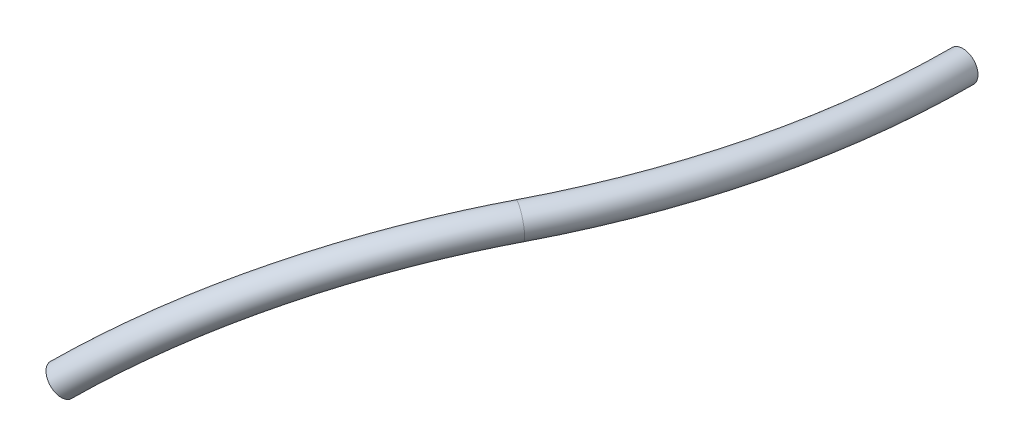
SolidWorks part; units mm, degrees
ref_plane "Front" through (0, 0, 0) normal (0, 0, 1) x (1, 0, 0)
ref_plane "Top" through (0, 0, 0) normal (0, 1, 0) x (1, 0, 0)
ref_plane "Right" through (0, 0, 0) normal (1, 0, 0) x (0, 0, -1)
sketch "Sketch1" plane through (0, 0, 0) normal (0, 0, 1) x (1, 0, 0)
  circle A0 centre (3583.5486, 6892.4155) radius 50.8
ref_plane "Plane1" through (-767.9169, 6367.643, 0) normal (0.1197, -0.9928, 0) x (0, 0, -1)
sketch "Sketch2" plane through (-767.9169, 6367.643, 0) normal (0.1197, -0.9928, 0) x (0, 0, -1)
  line L0 (0, 4382.9942) -> (-326.2728, 4382.9942) construction
  line L1 (-1154.8874, 4046.4415) -> (-1434.4794, 3868.3634) construction
  line L2 (-1154.8874, 4046.4415) -> (0, 4382.9942) construction
  line L3 (-577.4437, 4214.7179) -> (-601.4633, 4297.1418) construction
  arc A0 (0, 4382.9942) -> (-1154.8874, 4046.4415) centre (0, 2233.2082) ccw
  point P6 (-609.9931, 4294.6369)
  dimension "D1" = 1219.2
  dimension "D2" = 600.71
  dimension "D4" = 1524
  dimension "D3" = 85.8524
ref_plane "Plane2" through (-508.8422, 360.2726, -294.2875) normal (0.7381, -0.5226, 0.4269) x (-0.6491, -0.7226, 0.2377)
sketch "Sketch3" plane through (-508.8422, 360.2726, -294.2875) normal (0.7381, -0.5226, 0.4269) x (-0.6491, -0.7226, 0.2377)
  line L0 (-6786.2097, -3509.4251) -> (-6589.5927, -3776.3058) construction
  line L1 (-5763.7034, -4110.8775) -> (-2094.3697, -4581.5268) construction
  line L2 (-6786.2097, -3509.4251) -> (-5763.7034, -4110.8775) construction
  line L3 (-6274.9565, -3810.1513) -> (-6336.565, -3914.8895) construction
  arc A0 (-6786.2097, -3509.4251) -> (-5763.7034, -4110.8775) centre (-5571.8009, -2614.7434) ccw
  point P7 (-5975.1562, -4068.2042)
  point P8 (-6663.8452, -3655.264)
  dimension "D1" = 1219.2
  dimension "D2" = 215.9
  dimension "D4" = 812.8
  dimension "D3" = 121.5141
sweep "Sweep1" add profiles "Sketch1" path "Sketch2"
sketch "Sketch4" plane through (639.8566, 77.1646, -1011.8871) normal (-0.5333, -0.0643, 0.8434) x (0.8459, -0.0406, 0.5318)
  circle A0 centre (3084.9615, 6920.0978) radius 50.8
sweep "Sweep2" add profiles "Sketch4" path "Sketch3"
ref_axis "Axis1" through (2790.8696, 6796.821, 1880.0468) along (0.5333, 0.0643, -0.8434)
ref_plane "Plane3" through (2609.5603, 6774.9557, 2166.7745) normal (0.5333, 0.0643, -0.8434) x (-0.8459, 0.0406, -0.5318)
ref_plane "Plane5" through (10869.8156, -9012.4784, 3172.3897) normal (0.7511, -0.6227, 0.2192) x (0.1687, -0.1399, -0.9757)
ref_point "Point1"
ref_axis "Axis2" through (10869.9203, -575.1812, 4372.8103) along (-0.7511, 0.6227, -0.2192)
ref_point "Point2"
ref_axis "Axis3" through (-4811.4788, 13852.9754, -2450.115) along (0.7511, -0.6227, 0.2192)
sketch "Sketch6" plane through (0, 0, 0) normal (0, 0, -1) x (-1, 0, 0)
  line L0 (-3615.9728, 6931.5219) -> (-3551.1244, 6853.3091)
  line L1 (4811.4788, 13852.9754) -> (-3583.5486, 6892.4155) construction
  line L2 (-3633.9832, 6898.4978) -> (-3533.114, 6886.3333)
  line L3 (645.0438, 6382.4611) -> (890.7901, 6352.8249) construction
  circle A0 centre (-3583.5486, 6892.4155) radius 50.8 construction
  point P6 (-3583.5486, 6892.4155)
  dimension "D1" = 43.46
